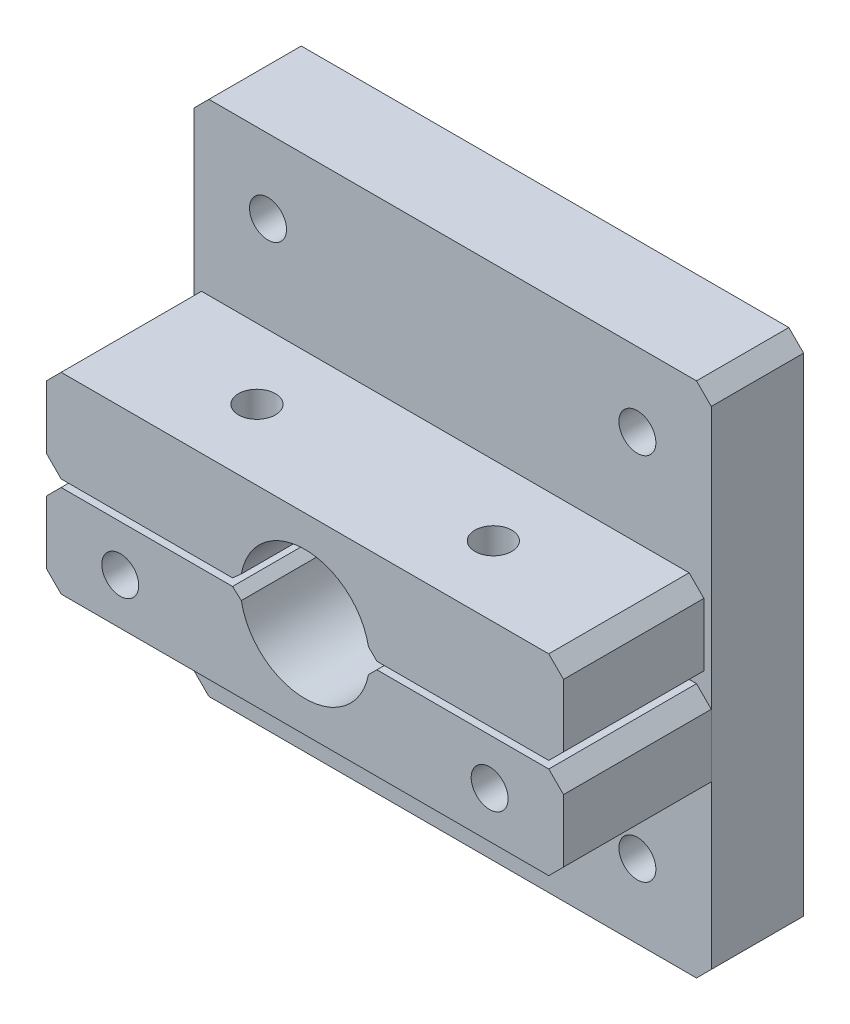
SolidWorks part; units mm, degrees
material "6061-T6 (SS)"
ref_plane "Front Plane" through (0, 0, 0) normal (0, 0, 1) x (1, 0, 0)
ref_plane "Top Plane" through (0, 0, 0) normal (0, 1, 0) x (1, 0, 0)
ref_plane "Right Plane" through (0, 0, 0) normal (1, 0, 0) x (0, 0, -1)
sketch "Sketch1" plane through (0, 0, 0) normal (0, 0, 1) x (1, 0, 0)
  line L0 (0, 44.45) -> (0, -44.45) construction
  line L1 (-44.45, 44.45) -> (44.45, 44.45)
  line L2 (-44.45, 44.45) -> (-44.45, -44.45)
  line L3 (-44.45, -44.45) -> (44.45, -44.45)
  line L4 (44.45, 44.45) -> (44.45, -44.45)
  line L5 (-44.45, 0) -> (44.45, 0) construction
  line L6 (-44.45, 0) -> (-44.45, -0.635)
  line L7 (-44.45, -0.635) -> (0, -0.635) construction
  line L8 (0, -0.635) -> (-11.0943, -0.635) construction
  line L9 (-11.0943, -0.635) -> (-44.45, -0.635)
  line L10 (-44.45, -0.635) -> (-44.45, -16.51)
  line L11 (-44.45, -16.51) -> (44.45, -16.51)
  line L12 (11.0943, -0.635) -> (44.45, -0.635)
  line L13 (44.45, -0.635) -> (44.45, -16.51)
  line L14 (11.0943, 0.635) -> (44.45, 0.635)
  line L15 (44.45, 0.635) -> (44.45, 16.51)
  line L16 (-44.45, 16.51) -> (44.45, 16.51)
  line L17 (-44.45, 0.635) -> (-44.45, 16.51)
  line L18 (-11.0943, 0.635) -> (-44.45, 0.635)
  line L19 (-44.45, -8.5725) -> (-31.75, -8.5725) construction
  line L20 (-31.75, -8.5725) -> (-31.75, -16.51) construction
  circle A0 centre (0, 0) radius 11.1125
  circle A1 centre (31.75, 31.75) radius 3.175
  circle A2 centre (-31.75, 31.75) radius 3.175
  circle A3 centre (31.75, -31.75) radius 3.175
  circle A4 centre (-31.75, -31.75) radius 3.175
  circle A5 centre (-31.75, -8.5725) radius 3.175
  circle A6 centre (31.75, -8.5725) radius 3.175
  circle A7 centre (0, 0) radius 4.7625
  circle A10 centre (0, 0) radius 4.7625 construction
  point P28 (0, -16.51)
  dimension "D1" = 22.225
  dimension "D5" = 6.35
  dimension "D2" = 88.9
  dimension "D3" = 12.7
  dimension "D4" = 12.7
  dimension "D6" = 0.635
  dimension "D7" = 16.51
  dimension "D8" = 88.9
  dimension "D9" = 12.7
extrude "Boss-Extrude1" add sketch "Sketch1" along normal blind 7.9375 contours L2 L16 L4 L1 A1 A2 | A0 L14 L4 L16 L2 L18 | A0 L9 L2 L11 L4 L12 A5 A6 | L11 L2 L3 L4 A4 A3 | A0 L18 L2 L9 | A0 L12 L4 L14 region at (0, 30.4468, 0) region at (0, 15.6069, 0) region at (-27.7782, 0, 0) region at (27.7782, 0, 0) region at (43.5469, -8.5725, 0) region at (0, -30.4468, 0)
extrude "Boss-Extrude2" add sketch "Sketch1<3>" along normal blind 25.4 from surface separate body contours A0 L9 L10 L11 L13 L12 region at (43.5469, -8.5725, 0) starting at face at (0, 0, 7.9375)
sketch "Sketch1<3>" plane through (0, 0, 0) normal (0, 0, 1) x (1, 0, 0) same geometry as "Sketch1"
extrude "Boss-Extrude3" add sketch "Sketch1<4>" against normal blind 24.13 from surface separate body contours A0 L14 L15 L16 L17 L18 region at (0, 15.6069, 0) starting at face at (-28.575, -8.5725, 33.3375)
sketch "Sketch1<4>" plane through (0, 0, 0) normal (0, 0, 1) x (1, 0, 0) same geometry as "Sketch1"
sketch "Sketch2" plane through (0, 0, 0) normal (0, 1, 0) x (1, 0, 0)
  line L0 (0, 0) -> (0, -7.9375)
  line L1 (0, -7.9375) -> (0, -9.2075)
  line L2 (0, -21.2725) -> (20.32, -21.2725)
  line L3 (0, -9.2075) -> (0, -33.3375)
  circle A0 centre (20.32, -21.2725) radius 3.175
  circle A2 centre (0, -21.2725) radius 1.5875
  circle A3 centre (-20.32, -21.2725) radius 3.175
  point P5 (0, 0)
  dimension "D1" = 7.9375
  dimension "D3" = 6.35
  dimension "D4" = 3.175
  dimension "D2" = 1.27
  dimension "D6" = 20.32
extrude "Cut-Extrude1" cut sketch "Sketch2" against normal through all both and the other way through all contours A3 | A0 region at (20.32, 0, 18.1873) region at (-20.32, 0, 21.2725)
extrude "Boss-Extrude4" add sketch "Sketch1<5>" against normal blind 7.9375 contours L11 L2 L3 L4 A4 A3 | A0 L9 L2 L11 L4 L12 A5 A6 | A0 L12 L4 L14 | A0 L14 L4 L16 L2 L18 | L2 L16 L4 L1 A1 A2 | A0 L18 L2 L9 | A7 | A0 region at (0, 30.4468, 0) region at (0, 15.6069, 0) region at (-27.7782, 0, 0) region at (27.7782, 0, 0) region at (43.5469, -8.5725, 0) region at (0, -30.4468, 0) region at (0, 0, 0)
sketch "Sketch1<5>" plane through (0, 0, 0) normal (0, 0, 1) x (1, 0, 0) same geometry as "Sketch1"
chamfer "Chamfer1" distance 2.54 angle 45 4 edges at (-44.45, -44.45, 0) (44.45, -44.45, 0) (44.45, 44.45, 0) (-44.45, 44.45, 0)
chamfer "Chamfer2" distance 2.54 angle 45 4 edges at (44.45, -0.635, 20.6375) (-44.45, -0.635, 20.6375) (-44.45, -16.51, 20.6375) (44.45, -16.51, 20.6375)
chamfer "Chamfer3" distance 2.54 angle 45 4 edges at (-44.45, 0.635, 21.2725) (-44.45, 16.51, 21.2725) (44.45, 16.51, 21.2725) (44.45, 0.635, 21.2725)
chamfer "Chamfer4" distance 1.27 angle 45 2 edges at (11.0943, -0.635, 20.6375) (-11.0943, -0.635, 20.6375) first distance on face at (23.495, -0.635, 21.2725) first distance on face at (0, -5.8738, 20.6375)
chamfer "Chamfer5" distance 1.27 angle 45 2 edges at (-11.0943, 0.635, 21.2725) (11.0943, 0.635, 21.2725) first distance on face at (0, 5.8738, 21.2725) first distance on face at (17.145, 0.635, 21.2725)
equation "\"Shaft Diameter\"= 7 / 8"
equation "\"Overall Width\" = 3.5"
equation "\"Overall Height\" = \"Bracket Plate Thickness\" + 1"
equation "\"Bolt Diameter Plate\"= 1 / 4"
equation "\"Bolt Diameter Bracket\"= 1 / 4"
equation "\"D3@Sketch1\"=\"Bolt from edge\""
equation "\"D2@Sketch1\"=\"Overall Width\""
equation "\"D1@Sketch1\"=\"Shaft Diameter\""
equation "\"Bolt from edge\" = .5"
equation "\"D4@Sketch1\"=\"Bolt from edge\""
equation "\"D5@Sketch1\"=\"Bolt Diameter Plate\""
equation "\"Bracket Gap\"= .05"
equation "\"Bracket Plate Thickness\"= 5 / 8"
equation "\"D6@Sketch1\"=\"Bracket Gap\"/2"
equation "\"D7@Sketch1\"=\"Bracket Plate Thickness\"+\"Bracket Gap\"/2"
equation "\"D1@Boss-Extrude1\"=\"Bracket Plate Thickness\"/2"
equation "\"D1@Boss-Extrude2\"=\"Overall Height\"-\"Bracket Plate Thickness\""
equation "\"D3@Sketch2\"=\"Bolt Diameter Bracket\""
equation "\"D1@Boss-Extrude3\"=\"Overall Height\"-\"Bracket Plate Thickness\"-.05"
equation "\"Pin bolt diameter\"= 1 / 8"
equation "\"D4@Sketch2\"=\"Pin bolt diameter\""
equation "\"D9@Sketch1\"=\"Bolt from edge\""
equation "\"D1@Boss-Extrude4\"=\"Bracket Plate Thickness\"/2"
equation "\"D1@Sketch2\"=\"Bracket Plate Thickness\"/2"
equation "\"D2@Sketch2\"=\"Bracket Gap\""
